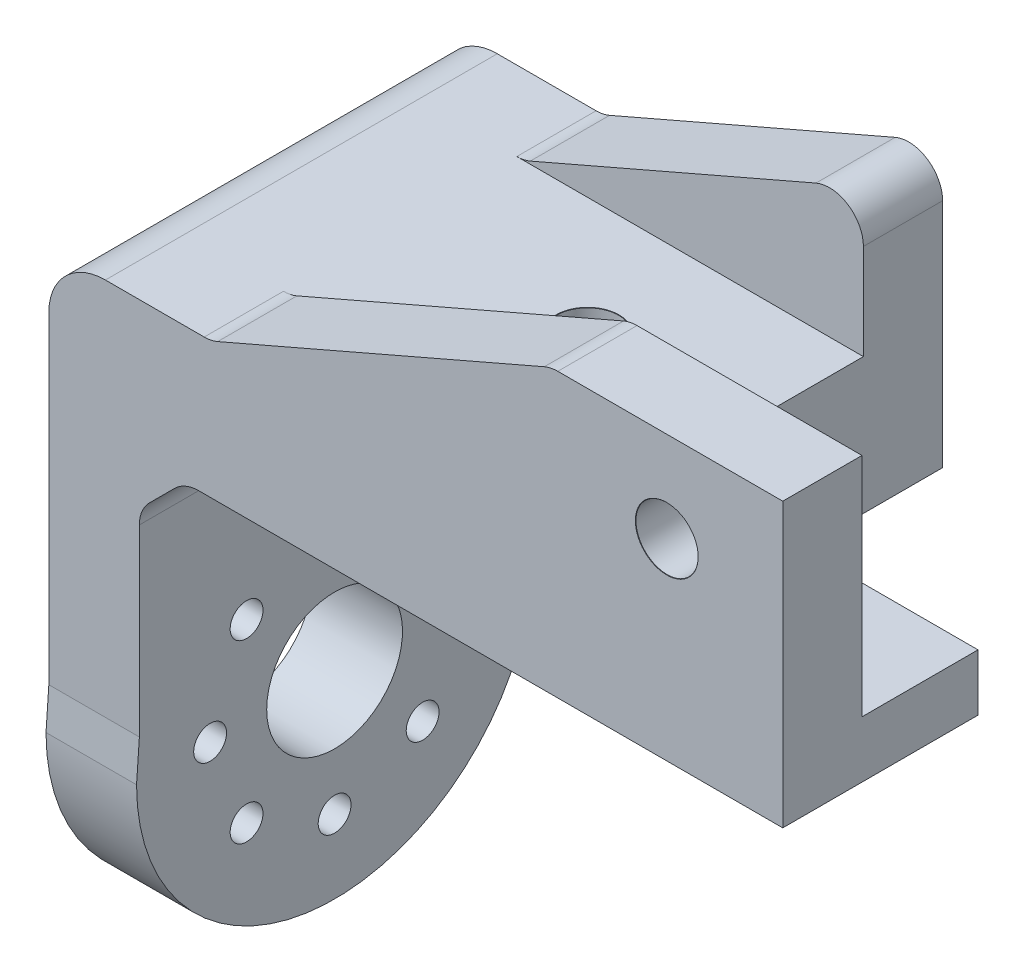
SolidWorks part; units mm, degrees
ref_plane "前视基准面" through (0, 0, 0) normal (0, 0, 1) x (1, 0, 0)
ref_plane "上视基准面" through (0, 0, 0) normal (0, 1, 0) x (1, 0, 0)
ref_plane "右视基准面" through (0, 0, 0) normal (1, 0, 0) x (0, 0, -1)
sketch "草图1" plane through (0, 0, 0) normal (0, 0, 1) x (1, 0, 0)
  line L0 (-2.4052, -0.0763) -> (-130.7806, -0.0763) construction
  line L1 (0, 0) -> (0, 37.5806) construction
  line L7 (50.6, -0.0763) -> (50.6, 29.9237)
  line L8 (50.6, 29.9237) -> (20, 59.9237)
  line L9 (20, 59.9237) -> (-20, 59.9237)
  line L10 (-20, 59.9237) -> (-50.6, 29.9237)
  line L11 (-50.6, 29.9237) -> (-50.6, -0.0763)
  line L12 (-50.6, -0.0763) -> (50.6, -0.0763)
  dimension "D1" = 101.2
  dimension "D2" = 60
  dimension "D5" = 30
  dimension "D6" = 40
extrude "凸台-拉伸1" add sketch "草图1" along normal blind 35
sketch "草图6" plane through (-50.6, 0, 0) normal (-1, 0, 0) x (0, 0, 1)
  line L0 (35, -0.0763) -> (0, -0.0763) construction
  circle A0 centre (17.5, -0.0763) radius 6
  dimension "D1" = 12
extrude "切除-拉伸2" cut sketch "草图6" against normal up to surface (101.2 mm away) up to face at (50.6, 14.9237, 17.5)
sketch "草图7" plane through (-50.6, 0, 0) normal (-1, 0, 0) x (0, 0, 1)
  line L0 (11.5, -0.0763) -> (0, -0.0763) construction
  line L1 (35, -0.0763) -> (23.5, -0.0763) construction
  circle A0 centre (5.75, -0.0763) radius 5.75
  circle A1 centre (29.25, -0.0763) radius 5.75
extrude "凸台-拉伸3" add sketch "草图7" against normal up to surface (101.2 mm away) up to face at (50.6, 10.9237, 17.5)
sketch "草图8" plane through (0, 0, 35) normal (0, 0, 1) x (1, 0, 0)
  line L0 (0, -0.0763) -> (0, 61.1377) construction
  line L2 (-46.6, -0.0763) -> (-46.6, 24.9237)
  line L3 (-50.6, -0.0763) -> (50.6, -0.0763) construction
  line L4 (-46.6, 24.9237) -> (46.6, 24.9237)
  line L5 (46.6, 24.9237) -> (46.6, -0.0763)
  line L7 (-46.6, -0.0763) -> (-46.6, -12.1113)
  line L8 (-46.6, -12.1113) -> (46.6, -12.1113)
  line L9 (46.6, -12.1113) -> (46.6, -0.0763)
  dimension "D1" = 93.2
  dimension "D2" = 25
extrude "切除-拉伸3" cut sketch "草图8" against normal up to surface (35 mm away) up to face at (0, 29.9237, 0)
sketch "草图16" plane through (0, 59.9237, 0) normal (0, 1, 0) x (1, 0, 0)
  line L0 (0, 0) -> (0, -35) construction
  line L3 (-20, -17.5) -> (20, -17.5) construction
  line L4 (-10.1, -7.4) -> (10.1, -7.4)
  line L5 (-10.1, -7.4) -> (-10.1, -27.6)
  line L6 (-10.1, -27.6) -> (10.1, -27.6)
  line L7 (10.1, -7.4) -> (10.1, -27.6)
  dimension "D1" = 20.2
  dimension "D2" = 20.2
extrude "切除-拉伸5" cut sketch "草图16" against normal blind 30
sketch "草图15" plane through (0, 0, 35) normal (0, 0, 1) x (1, 0, 0)
  line L0 (0, 24.9237) -> (0, 61.498) construction
  line L2 (0, 24.9237) -> (-10.25, 24.9237)
  line L3 (46.6, 24.9237) -> (-46.6, 24.9237) construction
  line L4 (-10.25, 24.9237) -> (-10.25, 59.9237)
  line L5 (20, 59.9237) -> (-20, 59.9237) construction
  line L6 (-10.25, 59.9237) -> (10.25, 59.9237)
  line L7 (10.25, 59.9237) -> (10.25, 24.9237)
  line L8 (10.25, 24.9237) -> (-10.25, 24.9237)
  dimension "D1" = 20.5
extrude "切除-拉伸6" cut sketch "草图15" against normal blind 4.25 contours L4 L6 L7 L8
sketch "草图17" plane through (0, 0, 0) normal (0, 0, -1) x (-1, 0, 0)
  line L4 (-10.25, 24.9237) -> (10.25, 24.9237)
  line L5 (-10.25, 59.9237) -> (-10.25, 24.9237)
  line L6 (10.25, 59.9237) -> (-10.25, 59.9237)
  line L7 (10.25, 24.9237) -> (10.25, 59.9237)
  line L8 (-10.25, 24.9237) -> (10.25, 24.9237)
  line L9 (-10.25, 59.9237) -> (-10.25, 24.9237)
  line L10 (10.25, 59.9237) -> (-10.25, 59.9237)
  line L11 (10.25, 24.9237) -> (10.25, 59.9237)
  dimension "D1" = 0
extrude "切除-拉伸7" cut sketch "草图17" against normal blind 4.25
hole_wizard "M5 Clearance Hole1" [suppressed] positions "草图18" profile "草图19" hole size "M5" standard "ISO"
sketch "草图18" plane through (0, 0, 4.25) normal (0, 0, -1) x (-1, 0, 0)
  line L0 (0, 24.9237) -> (0, 65.7443) construction
  line L3 (0, 29.9237) -> (-37.1771, 29.9237) construction
  line L5 (-10.25, 24.9237) -> (10.25, 24.9237) construction
  point P18 (0, 35.9237)
  point P20 (0, 50.9237)
  dimension "D1" = 5
  dimension "D2" = 15
  dimension "D3" = 6
sketch "草图19" plane through (0, 50.9237, 4.25) normal (1, 0, 0) x (0, 1, 0)
  line L0 (0, 0) -> (0, 30.75)
  line L1 (0, 30.75) -> (2.75, 30.75)
  line L2 (2.75, 30.75) -> (2.75, 0.025)
  line L3 (2.75, 0.025) -> (2.775, 0)
  line L5 (2.775, 0) -> (0, 0)
  line L6 (-2.75, 0.025) -> (-2.775, 0) construction
  line L11 (0, -6.35) -> (0, 107.95) construction
  dimension "通孔孔直径" = 5.5
  dimension "通孔孔深度" = 30.75
  dimension "近端锥形沉头孔直径" = 5.55
  dimension "近端锥形沉头孔角度" = 90
sketch "草图20" plane through (50.6, 0, 0) normal (1, 0, 0) x (0, 0, -1)
  line L0 (-30.75, 59.9237) -> (-35, 59.9237) construction
  line L1 (-30.75, 59.9237) -> (-35, 59.9237)
  line L2 (-30.75, 59.9237) -> (-35, -0.0763)
  line L3 (-35, -0.0763) -> (-35, 59.9237)
  line L4 (-17.5, 59.9237) -> (-17.5, 49.5416) construction
  line L6 (0, -0.0763) -> (0, 59.9237)
  line L7 (-4.25, 59.9237) -> (0, -0.0763)
  line L8 (-4.25, 59.9237) -> (0, 59.9237)
extrude "切除-拉伸8" cut sketch "草图20" against normal up to surface (101.2 mm away) up to face at (-50.6, 9.0071, 17.5)
sketch "草图21" plane through (50.6, 0, 0) normal (1, 0, 0) x (0, 0, -1)
  line L0 (-27.6, 59.9237) -> (-29.725, 29.9237)
  line L1 (-17.5, 59.9237) -> (-17.5, 29.9237) construction
  line L3 (-32.875, 29.9237) -> (-2.125, 29.9237) construction
  line L4 (-29.725, 29.9237) -> (-5.275, 29.9237)
  line L5 (-27.6, 59.9237) -> (-7.4, 59.9237)
  line L6 (-30.75, 59.9237) -> (-4.25, 59.9237) construction
  line L7 (-7.4, 59.9237) -> (-5.275, 29.9237)
  line L8 (-30.75, 59.9237) -> (-32.875, 29.9237) construction
  point P10 (-17.5, 29.9237)
  point P11 (-17.5, 59.9237)
  dimension "D1" = 0
extrude "切除-拉伸9" cut sketch "草图21" against normal blind 36.25 contours L4 L7 L5 L0
sketch "草图22" plane through (-50.6, 0, 0) normal (-1, 0, 0) x (0, 0, 1)
  line L4 (29.725, 29.9237) -> (27.6, 59.9237)
  line L5 (5.275, 29.9237) -> (29.725, 29.9237)
  line L6 (7.4, 59.9237) -> (5.275, 29.9237)
  line L7 (27.6, 59.9237) -> (7.4, 59.9237)
  line L8 (29.725, 29.9237) -> (27.6, 59.9237)
  line L9 (5.275, 29.9237) -> (29.725, 29.9237)
  line L10 (7.4, 59.9237) -> (5.275, 29.9237)
  line L11 (27.6, 59.9237) -> (7.4, 59.9237)
  dimension "D1" = 0
extrude "切除-拉伸10" cut sketch "草图22" against normal blind 36.25
sketch "草图23" [suppressed] plane through (-15.35, 0, 0) normal (-1, 0, 0) x (0, 0, 1)
  line L0 (17.5, 59.9237) -> (17.5, 29.9237) construction
  line L3 (13.5, 34.9237) -> (21.5, 34.9237)
  line L4 (10.5, 37.9237) -> (10.5, 51.9237)
  line L5 (17.65, 44.9237) -> (-13.119, 44.9237) construction
  line L6 (5.275, 29.9237) -> (29.725, 29.9237) construction
  line L7 (13.5, 54.9237) -> (21.5, 54.9237)
  line L8 (24.5, 37.9237) -> (24.5, 51.9237)
  arc A0 (10.5, 37.9237) -> (13.5, 34.9237) centre (13.5, 37.9237) ccw
  arc A1 (10.5, 31.9237) -> (13.5, 34.9237) centre (13.5, 31.9237) cw
  arc A2 (10.5, 51.9237) -> (13.5, 54.9237) centre (13.5, 51.9237) cw
  arc A3 (24.5, 37.9237) -> (21.5, 34.9237) centre (21.5, 37.9237) cw
  arc A4 (24.5, 51.9237) -> (21.5, 54.9237) centre (21.5, 51.9237) ccw
  point P20 (10.5, 44.9237)
  point P21 (17.5, 34.9237)
  point P26 (17.5, 54.9237)
  dimension "D1" = 3
  dimension "D2" = 15
  dimension "D3" = 7
  dimension "D4" = 4
extrude "切除-拉伸11" [suppressed] cut sketch "草图23" against normal up to surface (30.7 mm away) contours L3 A3 L8 A4 L7 A2 L4 A0
sketch "草图25" plane through (0, 0, 0) normal (0, 0, 1) x (1, 0, 0)
  line L0 (14.35, 59.9237) -> (20, 59.9237) construction
  line L1 (14.35, 59.9237) -> (14.35, 29.9237) construction
  line L2 (14.35, 29.9237) -> (50.6, 29.9237) construction
  line L3 (14.35, 59.9237) -> (20, 59.9237) construction
  line L4 (14.35, 59.9237) -> (14.35, 29.9237) construction
  line L5 (14.35, 29.9237) -> (50.6, 29.9237) construction
  line L6 (38.35, 33.9237) -> (18.35, 33.9237)
  line L7 (18.35, 33.9237) -> (18.35, 53.5316)
  line L8 (18.35, 53.5316) -> (38.35, 33.9237)
  line L9 (0, 59.9237) -> (0, 24.9237) construction
  line L10 (14.35, 29.9237) -> (50.6, 29.9237)
  line L11 (14.35, 59.9237) -> (14.35, 29.9237)
  line L12 (20, 59.9237) -> (14.35, 59.9237)
  line L13 (50.6, 29.9237) -> (20, 59.9237)
  line L14 (14.35, 29.9237) -> (50.6, 29.9237) construction
  line L15 (14.35, 59.9237) -> (14.35, 29.9237) construction
  line L16 (20, 59.9237) -> (14.35, 59.9237) construction
  line L17 (50.6, 29.9237) -> (20, 59.9237) construction
  line L18 (-18.35, 53.5316) -> (-38.35, 33.9237)
  line L19 (-18.35, 33.9237) -> (-18.35, 53.5316)
  line L20 (-38.35, 33.9237) -> (-18.35, 33.9237)
  dimension "D2" = 4
  dimension "D3" = 4
  dimension "D4" = 20
  dimension "D1" = 0
extrude "切除-拉伸12" cut sketch "草图25" along normal through all
ref_plane "Plane1" through (0, 0, 0) normal (1, 0, 0) x (0, 0, -1)
sketch "Sketch1" plane through (50.6, 0, 0) normal (1, 0, 0) x (0, 0, -1)
  line L0 (-29.725, 29.9237) -> (-5.275, 29.9237) construction
  line L1 (7.5, -10.0763) -> (-42.5, -10.0763)
  line L2 (7.5, -10.0763) -> (7.5, 69.9237)
  line L3 (7.5, 69.9237) -> (-42.5, 69.9237)
  line L4 (-42.5, -10.0763) -> (-42.5, 69.9237)
  line L5 (7.5, -10.0763) -> (-42.5, 69.9237) construction
  line L6 (7.5, 69.9237) -> (-42.5, -10.0763) construction
  point P0 (-17.5, 29.9237)
  dimension "D1" = 50
  dimension "D2" = 80
extrude "Cut-Extrude1" cut sketch "Sketch1" against normal up to surface (50.6 mm away) up to plane "Plane1"
sketch "Sketch2" plane through (-14.35, 0, 0) normal (-1, 0, 0) x (0, 0, 1)
  line L0 (17.5, 29.9237) -> (17.5, 59.9237) construction
  line L1 (5.275, 29.9237) -> (29.725, 29.9237) construction
  line L2 (27.6, 59.9237) -> (7.4, 59.9237) construction
  point P6 (17.5, 51.9237)
  point P7 (17.5, 36.9237)
  dimension "D1" = 15
  dimension "D2" = 7
hole_wizard "M5 Clearance Hole2" positions "Sketch2" profile "Sketch3" hole size "M5" standard "ISO" end condition through all
sketch "Sketch3" plane through (-14.35, 36.9237, 17.5) normal (0, 1, 0) x (0, 0, 1)
  line L0 (0, 0) -> (0, 14.35)
  line L1 (0, 14.35) -> (2.75, 14.35)
  line L2 (2.75, 14.35) -> (2.75, 0.025)
  line L3 (2.75, 0.025) -> (2.775, 0)
  line L5 (2.775, 0) -> (0, 0)
  line L6 (-2.75, 0.025) -> (-2.775, 0) construction
  line L11 (0, -6.35) -> (0, 107.95) construction
  dimension "Thru Hole Dia." = 5.5
  dimension "Thru Hole Depth" = 14.35
  dimension "Near C'Sink Dia." = 5.55
  dimension "Near C'Sink Angle" = 90
sketch "草图26" plane through (0, 0, 0) normal (1, 0, 0) x (0, 0, -1)
  line L0 (-5.275, 29.9237) -> (-29.725, 29.9237) construction
  line L1 (-56.2329, 29.9237) -> (16.1346, 29.9237)
  line L2 (-56.2329, 29.9237) -> (-56.2329, 60.1918)
  line L3 (-56.2329, 60.1918) -> (16.1346, 60.1918)
  line L4 (16.1346, 29.9237) -> (16.1346, 60.1918)
extrude "切除-拉伸13" cut sketch "草图26" against normal up to vertex
sketch "草图27" plane through (0, 29.9237, 0) normal (0, 1, 0) x (1, 0, 0)
  line L0 (-10.25, -2.125) -> (-10.25, -32.875)
  line L8 (-10.25, -30.75) -> (0, -30.75)
  line L9 (0, -30.75) -> (0, -4.25)
  line L10 (0, -4.25) -> (-10.25, -4.25)
  line L11 (-10.25, -4.25) -> (-10.25, -2.125)
  line L12 (-10.25, -2.125) -> (-50.6, -2.125)
  line L13 (-50.6, -2.125) -> (-50.6, -32.875)
  line L14 (-50.6, -32.875) -> (-10.25, -32.875)
  line L15 (-10.25, -32.875) -> (-10.25, -30.75)
  line L20 (-10.25, -2.125) -> (-50.6, -2.125)
  line L21 (-50.6, -2.125) -> (-50.6, -32.875)
  line L22 (-50.6, -32.875) -> (-10.25, -32.875)
  dimension "D1" = 0
extrude "凸台-拉伸4" add sketch "草图27" along normal blind 7
sketch "草图28" plane through (-50.6, 0, 0) normal (-1, 0, 0) x (0, 0, 1)
  line L5 (35, -0.0763) -> (32.875, 29.9237)
  line L6 (32.875, 29.9237) -> (32.875, 36.9237)
  line L7 (32.875, 36.9237) -> (2.125, 36.9237)
  line L8 (2.125, 36.9237) -> (2.125, 29.9237)
  line L9 (2.125, 29.9237) -> (0, -0.0763)
  line L10 (35, -0.0763) -> (32.875, 29.9237)
  line L11 (32.875, 29.9237) -> (32.875, 36.9237)
  line L12 (32.875, 36.9237) -> (2.125, 36.9237)
  line L13 (2.125, 36.9237) -> (2.125, 29.9237)
  line L14 (2.125, 29.9237) -> (0, -0.0763)
  arc A3 (23.5, -0.0763) -> (35, -0.0763) centre (29.25, -0.0763) ccw
  arc A4 (0, -0.0763) -> (11.5, -0.0763) centre (5.75, -0.0763) ccw
  arc A5 (23.5, -0.0763) -> (11.5, -0.0763) centre (17.5, -0.0763) ccw
  arc A6 (23.5, -0.0763) -> (35, -0.0763) centre (29.25, -0.0763) ccw
  arc A7 (0, -0.0763) -> (11.5, -0.0763) centre (5.75, -0.0763) ccw
  arc A8 (23.5, -0.0763) -> (11.5, -0.0763) centre (17.5, -0.0763) ccw
  dimension "D1" = 0
extrude "凸台-拉伸5" add sketch "草图28" along normal blind 4
sketch "草图36" plane through (-54.6, 0, 0) normal (-1, 0, 0) x (0, 0, 1)
  arc A0 (11.5, -0.0763) -> (23.5, -0.0763) centre (17.5, -0.0763) ccw
  arc A2 (0, -0.0763) -> (35, -0.0763) centre (17.5, -0.0763) ccw
  arc A3 (23.5, -0.0763) -> (35, -0.0763) centre (29.25, -0.0763) ccw construction
  arc A4 (0, -0.0763) -> (11.5, -0.0763) centre (5.75, -0.0763) ccw construction
  arc A5 (0, -0.0763) -> (11.5, -0.0763) centre (5.75, -0.0763) ccw
  arc A6 (23.5, -0.0763) -> (35, -0.0763) centre (29.25, -0.0763) ccw
extrude "凸台-拉伸8" add sketch "草图36" against normal blind 8
hole_wizard "M2.5 间隙孔1" positions "草图12" profile "草图13" hole size "M2.5" standard "ISO" end condition through all
sketch "草图12" plane through (-54.6, 0, 0) normal (1, 0, 0) x (0, 0, -1)
  line L0 (-17.5, 29.9237) -> (-17.5, -2.5018) construction
  circle A1 centre (-17.5, -0.0763) radius 0.7969 construction
  point P73 (-17.5, 10.9237)
  point P81 (-25.2782, 7.7019)
  point P88 (-9.7218, 7.7019)
  point P89 (-6.5, -0.0763)
  point P90 (-9.7218, -7.8545)
  point P91 (-17.5, -11.0763)
  point P92 (-25.2782, -7.8545)
  point P93 (-28.5, -0.0763)
  point P94 (-25.2782, 7.7019)
  dimension "D3" = 11
sketch "草图13" plane through (-54.6, 7.7019, 25.2782) normal (0, 1, 0) x (0, 0, 1)
  line L0 (0, 0) -> (0, 54.6)
  line L1 (0, 54.6) -> (1.45, 54.6)
  line L2 (1.45, 54.6) -> (1.45, 0.025)
  line L3 (1.45, 0.025) -> (1.475, 0)
  line L5 (1.475, 0) -> (0, 0)
  line L6 (-1.45, 0.025) -> (-1.475, 0) construction
  line L11 (0, -6.35) -> (0, 107.95) construction
  dimension "通孔孔直径" = 2.9
  dimension "通孔孔深度" = 54.6
  dimension "近端锥形沉头孔直径" = 2.95
  dimension "近端锥形沉头孔角度" = 90
fillet "圆角1" radius 5 1 edges at (-54.6, 36.9237, 17.5)
sketch "草图31" plane through (0, 0, 0) normal (1, 0, 0) x (0, 0, -1)
  line L23 (-1.7708, 24.9237) -> (-33.2292, 24.9237) construction
  line L24 (-30.75, 29.9237) -> (-17.5, 29.9237)
  line L25 (-30.75, 29.9237) -> (-30.75, 24.9237)
  line L26 (-30.75, 24.9237) -> (-17.5, 24.9237)
  line L27 (-17.5, 29.9237) -> (-17.5, 24.9237)
extrude "凸台-拉伸6" add sketch "草图31" along normal blind 10.25
sketch "草图32" plane through (0, 0, 0) normal (1, 0, 0) x (0, 0, -1)
  line L4 (-17.5, 29.9237) -> (-17.5, 24.9237)
  line L5 (-17.5, 24.9237) -> (-4.25, 24.9237)
  line L6 (-4.25, 24.9237) -> (-4.25, 29.9237)
  line L7 (-4.25, 29.9237) -> (-17.5, 29.9237)
  line L9 (-17.5, 24.9237) -> (-4.25, 24.9237)
  line L10 (-4.25, 24.9237) -> (-4.25, 29.9237)
  line L11 (-4.25, 29.9237) -> (-17.5, 29.9237)
  line L16 (-17.5, 29.9237) -> (-17.5, 24.9237)
  dimension "D1" = 0
extrude "切除-拉伸14" cut sketch "草图32" against normal up to surface (10.25 mm away) up to face at (-10.25, 29.3237, 17.5)
sketch "草图33" plane through (0, 29.9237, 0) normal (0, 1, 0) x (1, 0, 0)
  line L0 (-10.25, -32.875) -> (-10.25, -2.125) construction
  line L1 (10.25, -30.75) -> (-40.25, -30.75)
  line L2 (10.25, -30.75) -> (10.25, -27.75)
  line L3 (10.25, -27.75) -> (-40.25, -27.75)
  line L4 (-40.25, -30.75) -> (-40.25, -27.75)
  line L7 (10.25, -30.75) -> (-10.25, -30.75) construction
  dimension "D1" = 30
  dimension "D2" = 3
extrude "凸台-拉伸7" add sketch "草图33" along normal blind 20
sketch "草图34" plane through (0, 0, 30.75) normal (0, 0, 1) x (1, 0, 0)
  line L0 (-40.25, 36.9237) -> (-10.25, 49.9237)
  line L1 (-40.25, 49.9237) -> (10.25, 49.9237) construction
  line L2 (-10.25, 49.9237) -> (-40.25, 49.9237)
  line L3 (-40.25, 49.9237) -> (-40.25, 36.9237)
extrude "切除-拉伸15" cut sketch "草图34" against normal up to surface (3 mm away) up to face at (-13.4167, 38.9237, 27.75)
hole_wizard "M5 间隙孔2" positions "草图29" profile "草图30" hole size "M5" standard "ISO" end condition through all
sketch "草图29" plane through (0, 36.9237, 0) normal (0, 1, 0) x (1, 0, 0)
  line L0 (-41.2575, -17.5) -> (-9.6436, -17.5) construction
  line L3 (-10.25, -27.75) -> (-10.25, -17.5) construction
  point P0 (-24.25, -17.5)
  dimension "D1" = 14
sketch "草图30" plane through (-24.25, 36.9237, 17.5) normal (1, 0, 0) x (0, 0, 1)
  line L0 (0, 0) -> (0, 54.5)
  line L1 (0, 54.5) -> (2.75, 54.5)
  line L2 (2.75, 54.5) -> (2.75, 0.025)
  line L3 (2.75, 0.025) -> (2.775, 0)
  line L5 (2.775, 0) -> (0, 0)
  line L6 (-2.75, 0.025) -> (-2.775, 0) construction
  line L11 (0, -6.35) -> (0, 107.95) construction
  dimension "通孔孔直径" = 5.5
  dimension "通孔孔深度" = 54.5
  dimension "近端锥形沉头孔直径" = 5.55
  dimension "近端锥形沉头孔角度" = 90
sketch "草图43" plane through (0, 0, 30.75) normal (0, 0, 1) x (1, 0, 0)
  line L1 (-49.6, 36.9237) -> (-40.25, 36.9237)
  line L4 (-10.25, 36.9237) -> (-49.6, 36.9237)
  line L5 (-54.6, 31.9237) -> (-54.6, 29.9237)
  line L6 (10.25, 49.9237) -> (-10.25, 49.9237)
  line L7 (-10.25, 49.9237) -> (-40.25, 36.9237)
  line L8 (-40.25, 36.9237) -> (-10.25, 36.9237)
  line L9 (-10.25, 36.9237) -> (-10.25, 24.9237)
  line L11 (-10.25, 24.9237) -> (10.25, 24.9237)
  line L12 (10.25, 49.9237) -> (-10.25, 49.9237)
  line L13 (-10.25, 49.9237) -> (-40.25, 36.9237)
  line L18 (-54.6, 29.9237) -> (-10.25, 29.9237)
  line L19 (-10.25, 29.9237) -> (-10.25, 36.9237)
  line L21 (-54.6, 31.9237) -> (-54.6, 29.9237)
  line L26 (-10.25, 24.9237) -> (-10.25, 29.9237)
  line L27 (-10.25, 29.9237) -> (-54.6, 29.9237)
  line L28 (-54.6, 29.9237) -> (-54.6, -0.0763)
  line L29 (-54.6, -0.0763) -> (-46.6, -0.0763)
  line L30 (-46.6, -0.0763) -> (-46.6, 24.9237)
  line L31 (-46.6, 24.9237) -> (-10.25, 24.9237)
  line L34 (-54.6, 29.9237) -> (-54.6, -0.0763)
  line L35 (-54.6, -0.0763) -> (-46.6, -0.0763)
  line L36 (-46.6, -0.0763) -> (-46.6, 24.9237)
  line L37 (-46.6, 24.9237) -> (-10.25, 24.9237)
  line L40 (-10.25, 24.9237) -> (10.25, 24.9237)
  line L41 (10.25, 24.9237) -> (10.25, 49.9237)
  line L42 (10.25, 24.9237) -> (10.25, 49.9237)
  arc A3 (-49.6, 36.9237) -> (-54.6, 31.9237) centre (-49.6, 31.9237) ccw
  arc A5 (-49.6, 36.9237) -> (-54.6, 31.9237) centre (-49.6, 31.9237) ccw
  dimension "D1" = 0
  dimension "D2" = 0
  dimension "D3" = 0
extrude "凸台-拉伸10" add sketch "草图43" along normal blind 4
hole_wizard "M5 间隙孔1" positions "草图40" profile "草图41" hole size "M5" standard "ISO" end condition through all
sketch "草图40" plane through (0, 0, 34.75) normal (0, 0, 1) x (1, 0, 0)
  line L0 (10.25, 49.9237) -> (-10.25, 49.9237) construction
  point P5 (0, 41.9237)
  dimension "D1" = 8
sketch "草图41" plane through (0, 41.9237, 34.75) normal (1, 0, 0) x (0, -1, 0)
  line L0 (0, 0) -> (0, 34.75)
  line L1 (0, 34.75) -> (2.75, 34.75)
  line L2 (2.75, 34.75) -> (2.75, 0.025)
  line L3 (2.75, 0.025) -> (2.775, 0)
  line L5 (2.775, 0) -> (0, 0)
  line L6 (-2.75, 0.025) -> (-2.775, 0) construction
  line L11 (0, -6.35) -> (0, 107.95) construction
  dimension "通孔孔直径" = 5.5
  dimension "通孔孔深度" = 34.75
  dimension "近端锥形沉头孔直径" = 5.55
  dimension "近端锥形沉头孔角度" = 90
sketch "草图39" plane through (0, 24.9237, 0) normal (0, -1, 0) x (1, 0, 0)
  line L1 (-29.25, 22.5) -> (-19.25, 22.5)
  line L2 (-29.25, 22.5) -> (-29.25, 12.5)
  line L3 (-29.25, 12.5) -> (-19.25, 12.5)
  line L4 (-19.25, 22.5) -> (-19.25, 12.5)
  circle A0 centre (-24.25, 17.5) radius 2.75 construction
  dimension "D2" = 5
  dimension "D3" = 5
  dimension "D4" = 5
  dimension "D1" = 5
extrude "切除-拉伸17" cut sketch "草图39" against normal blind 4
chamfer "倒角1" distance 4 angle 45 1 edges at (-46.6, 24.9237, 18.2604)
sketch "草图46" plane through (0, -0.0754, 2.125) normal (0, 0, -1) x (-1, 0, 0)
  line L4 (54.6, 29.9991) -> (54.6, 31.9991)
  line L5 (49.6, 36.9991) -> (10.25, 36.9991)
  line L6 (10.25, 36.9991) -> (10.25, 29.9991)
  line L7 (10.25, 29.9991) -> (54.6, 29.9991)
  line L8 (54.6, 29.9991) -> (54.6, 31.9991)
  line L9 (49.6, 36.9991) -> (10.25, 36.9991)
  line L10 (10.25, 36.9991) -> (10.25, 29.9991)
  line L15 (46.6, -0.0009) -> (54.6, -0.0009)
  line L16 (54.6, -0.0009) -> (54.6, 29.9991)
  line L17 (54.6, 29.9991) -> (10.25, 29.9991)
  line L18 (10.25, 29.9991) -> (10.25, 24.9991)
  line L19 (10.25, 24.9991) -> (42.6, 24.9991)
  line L20 (42.6, 24.9991) -> (46.6, 20.9991)
  line L21 (46.6, 20.9991) -> (46.6, -0.0009)
  line L22 (46.6, -0.0009) -> (54.6, -0.0009)
  line L23 (54.6, -0.0009) -> (54.6, 29.9991)
  line L25 (10.25, 29.9991) -> (10.25, 24.9991)
  line L26 (10.25, 24.9991) -> (42.6, 24.9991)
  line L27 (42.6, 24.9991) -> (46.6, 20.9991)
  line L28 (46.6, 20.9991) -> (46.6, -0.0009)
  arc A1 (54.6, 31.9991) -> (49.6, 36.9991) centre (49.6, 31.9991) ccw
  arc A3 (54.6, 31.9991) -> (49.6, 36.9991) centre (49.6, 31.9991) ccw
  dimension "D1" = 0
  dimension "D2" = 0
extrude "凸台-拉伸15" add sketch "草图46" along normal blind 2
sketch "草图45" plane through (0, 0, 27.75) normal (0, 0, -1) x (-1, 0, 0)
  line L0 (10.25, 49.9237) -> (10.25, 36.9237)
  line L1 (10.25, 36.9237) -> (40.25, 36.9237)
  line L2 (40.25, 36.9237) -> (10.25, 49.9237)
extrude "凸台-拉伸16" add sketch "草图45" against normal blind 7 from surface at 27.625 starting at face at (-39.5169, 22.6193, 0.125)
fillet "圆角8" radius 3 6 edges at (-10.25, 49.9237, 31.25) (-42.6, 24.9237, 17.4375) (-46.6, 20.9237, 17.4375) (-40.25, 36.9237, 31.25) (-10.25, 49.9237, 3.625) (-40.25, 36.9237, 3.625)
